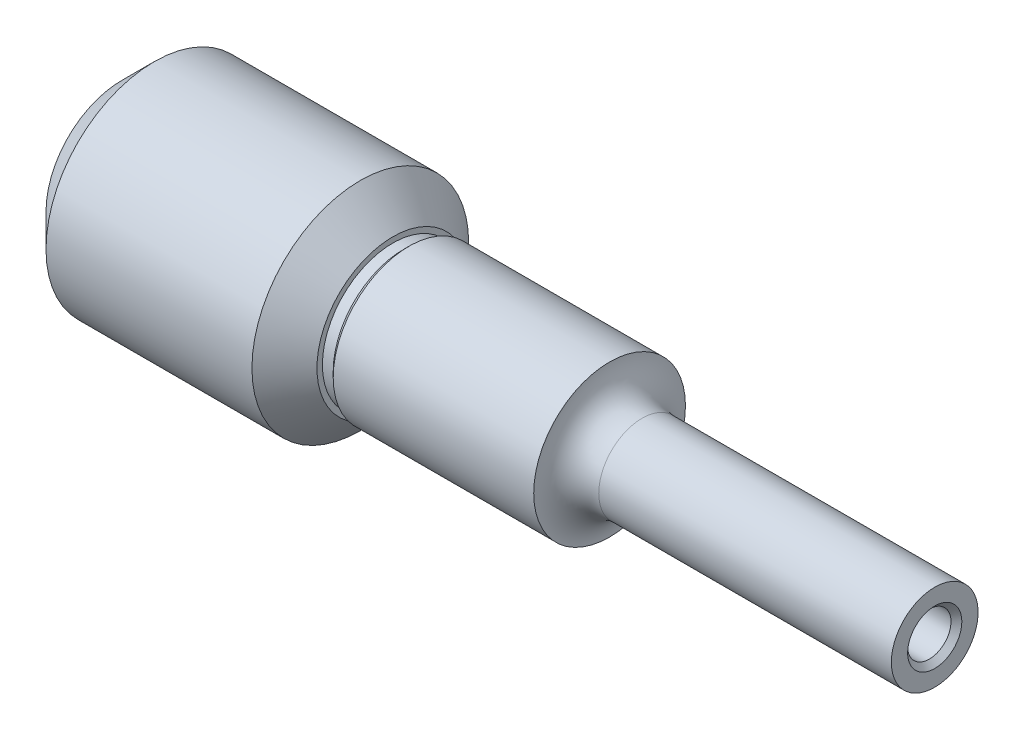
SolidWorks part; units mm, degrees
ref_plane "Front Plane" through (0, 0, 0) normal (0, 0, 1) x (1, 0, 0)
ref_plane "Top Plane" through (0, 0, 0) normal (0, 1, 0) x (1, 0, 0)
ref_plane "Right Plane" through (0, 0, 0) normal (1, 0, 0) x (0, 0, -1)
sketch "Sketch1" plane through (0, 0, 0) normal (0, 0, 1) x (1, 0, 0)
  line L0 (0, 0) -> (150, 0) construction
  line L5 (0, -10) -> (0, -20)
  line L6 (0, -10) -> (36, -10)
  line L7 (36, -10) -> (36, 0)
  line L8 (0, -20) -> (50, -20)
  line L9 (50, -13) -> (50, -20)
  line L10 (150, -4) -> (125, -4)
  line L11 (50, -13) -> (52, -13)
  line L12 (52, -13) -> (52, -14)
  line L13 (52, -14) -> (90, -14)
  line L14 (90, -14) -> (90, -8)
  line L15 (150, -4) -> (150, -8)
  line L16 (150, -8) -> (90, -8)
  line L17 (125, -4) -> (125, 0)
  line L18 (36, 0) -> (125, 0)
  point P14 (0, 0)
  point P18 (0, 0)
  point P19 (0, 0)
  point P20 (0, 0)
  dimension "D2" = 36
  dimension "D3" = 10
  dimension "D4" = 10
  dimension "D5" = 100
  dimension "D6" = 25
  dimension "D7" = 60
  dimension "D8" = 2
  dimension "D9" = 4
  dimension "D10" = 8
  dimension "D11" = 14
  dimension "D12" = 13
  dimension "D13" = 150
revolve "Revolve2" add sketch "Sketch1" angle 360 about L0
chamfer "Chamfer2" distance 6 angle 45 2 edges at (50, 0, 20) (0, 0, 20)
chamfer "Chamfer3" distance 3 angle 45 1 edges at (0, 0, 10)
chamfer "Chamfer4" distance 1 angle 45 1 edges at (150, 0, 4)
sketch "Sketch2" plane through (90, 0, 0) normal (1, 0, 0) x (0, 0, -1)
fillet "Fillet1" radius 6 1 edges at (90, 0, 8) type face fillet first side face at (90, 0, 8) second side face at (150, 0, 8)
chamfer "Chamfer5" distance 1 angle 45 1 edges at (52, 0, 14)
